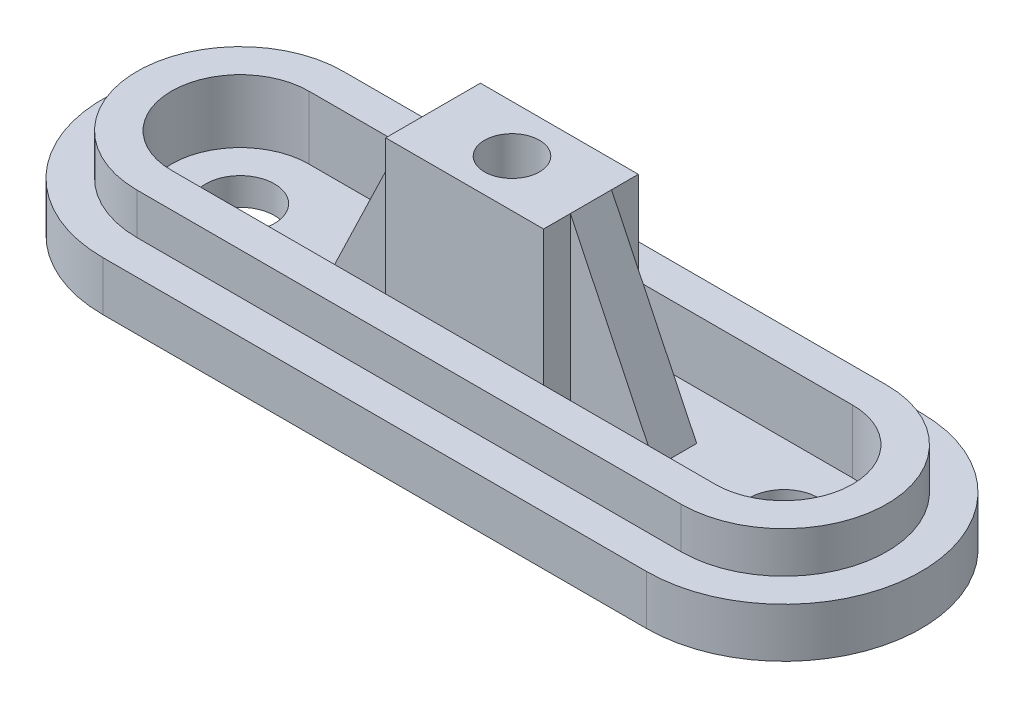
SolidWorks part; units mm, degrees
note: The reader was unsure of these and kept them because the rebuilt part matched: shared geometry of "Sketch1<6>", "Sketch1<7>", "Sketch1<8>", "Sketch1<10>".
ref_plane "Front Plane" through (0, 0, 0) normal (0, 0, 1) x (1, 0, 0)
ref_plane "Top Plane" through (0, 0, 0) normal (0, 1, 0) x (1, 0, 0)
ref_plane "Right Plane" through (0, 0, 0) normal (1, 0, 0) x (0, 0, -1)
sketch "Sketch1" plane through (0, 0, 0) normal (0, 1, 0) x (1, 0, 0)
  line L0 (0, 100) -> (0, -100) construction
  line L1 (0, -110) -> (0, 110) construction
  line L2 (-198, 0) -> (198, 0) construction
  line L3 (-198, 100) -> (198, 100)
  line L4 (-57.5, -34.5) -> (57.5, -34.5)
  line L5 (-57.5, -34.5) -> (-57.5, 34.5)
  line L6 (-57.5, 34.5) -> (57.5, 34.5)
  line L7 (57.5, -34.5) -> (57.5, 34.5)
  line L8 (-57.5, -34.5) -> (57.5, 34.5) construction
  line L9 (-57.5, 34.5) -> (57.5, -34.5) construction
  line L10 (-198, 75) -> (198, 75)
  line L11 (-198, 50) -> (198, 50)
  line L12 (-198, -50) -> (198, -50)
  line L13 (-198, -75) -> (198, -75)
  line L14 (-198, -100) -> (198, -100)
  line L15 (119.5, 15) -> (57.5, -15) construction
  line L16 (-119.5, -15) -> (-57.5, -15)
  line L17 (-119.5, -15) -> (-119.5, 15)
  line L18 (-119.5, 15) -> (-57.5, 15)
  line L19 (-57.5, -15) -> (-57.5, 15)
  line L20 (-119.5, -15) -> (-57.5, 15) construction
  line L21 (-119.5, 15) -> (-57.5, -15) construction
  line L22 (119.5, -15) -> (57.5, 15) construction
  line L23 (57.5, -15) -> (57.5, 15)
  line L24 (119.5, 15) -> (57.5, 15)
  line L25 (119.5, -15) -> (119.5, 15)
  line L26 (119.5, -15) -> (57.5, -15)
  line L27 (57.5, -34.5) -> (57.5, 34.5)
  circle A0 centre (-198, 0) radius 25
  circle A1 centre (0, 0) radius 20
  arc A5 (-198, 50) -> (-198, -50) centre (-198, 0) ccw
  arc A6 (-198, -75) -> (-198, 75) centre (-198, 0) cw
  arc A7 (-198, 100) -> (-198, -100) centre (-198, 0) ccw
  arc A8 (198, 100) -> (198, -100) centre (198, 0) cw
  arc A9 (198, -75) -> (198, 75) centre (198, 0) ccw
  arc A10 (198, 50) -> (198, -50) centre (198, 0) cw
  circle A11 centre (198, 0) radius 25
  point P7 (0, 0)
  point P8 (0, 0)
  point P20 (-88.5, 0)
  point P33 (0, -75)
  point P34 (0, -50)
  point P35 (0, 50)
  point P36 (0, 75)
  point P42 (88.5, 0)
  dimension "D3" = 50
  dimension "D4" = 40
  dimension "D7" = 50
  dimension "D1" = 239
  dimension "D2" = 396
  dimension "D5" = 69
  dimension "D6" = 115
  dimension "D8" = 75
  dimension "D9" = 100
  dimension "D10" = 30
extrude "Boss-Extrude2" add sketch "Sketch1" along normal blind 36 contours A8 L3 A7 L14 A9 L13 A6 L10
extrude "Boss-Extrude3" add sketch "Sketch1<6>" along normal blind 66 contours L13 A9 L10 A6 L11 A10 L12 A5
sketch "Sketch1<6>" plane through (0, 0, 0) normal (0, 1, 0) x (1, 0, 0) same geometry as "Sketch1"
extrude "Boss-Extrude4" add sketch "Sketch1<7>" along normal offset from surface (20 mm away) 46 contours A10 L11 A5 L12 A0 L25 L26 L7 L4 L5 L16 L17 L18 L6 L24 A11
sketch "Sketch1<7>" plane through (0, 0, 0) normal (0, 1, 0) x (1, 0, 0) same geometry as "Sketch1"
extrude "Boss-Extrude5" add sketch "Sketch1<8>" along normal blind 149 contours L4 L7 L6 L5 A1
sketch "Sketch1<8>" plane through (0, 0, 0) normal (0, 1, 0) x (1, 0, 0) same geometry as "Sketch1"
ref_point "Point3"
ref_point "Point4"
sketch "Sketch5" plane through (0, 0, 15) normal (0, 0, -1) x (-1, 0, 0)
  line L0 (119.5, 20) -> (57.5, 149)
extrude "Boss-Extrude6" add sketch "Sketch1<10>" along normal offset from surface (20 mm away) 46 contours L18 L17 L16 L5 | L26 L23 L24 L25 up to face at (0, 66, 0)
sketch "Sketch1<10>" plane through (0, 0, 0) normal (0, 1, 0) x (1, 0, 0) same geometry as "Sketch1"
rib "Rib2" sketch "Sketch5" sketch "Sketch5" thickness 30 parameters "D1"=30
mirror "Mirror1" about plane through (0, 0, 0) normal (1, 0, 0) of "Rib2"
